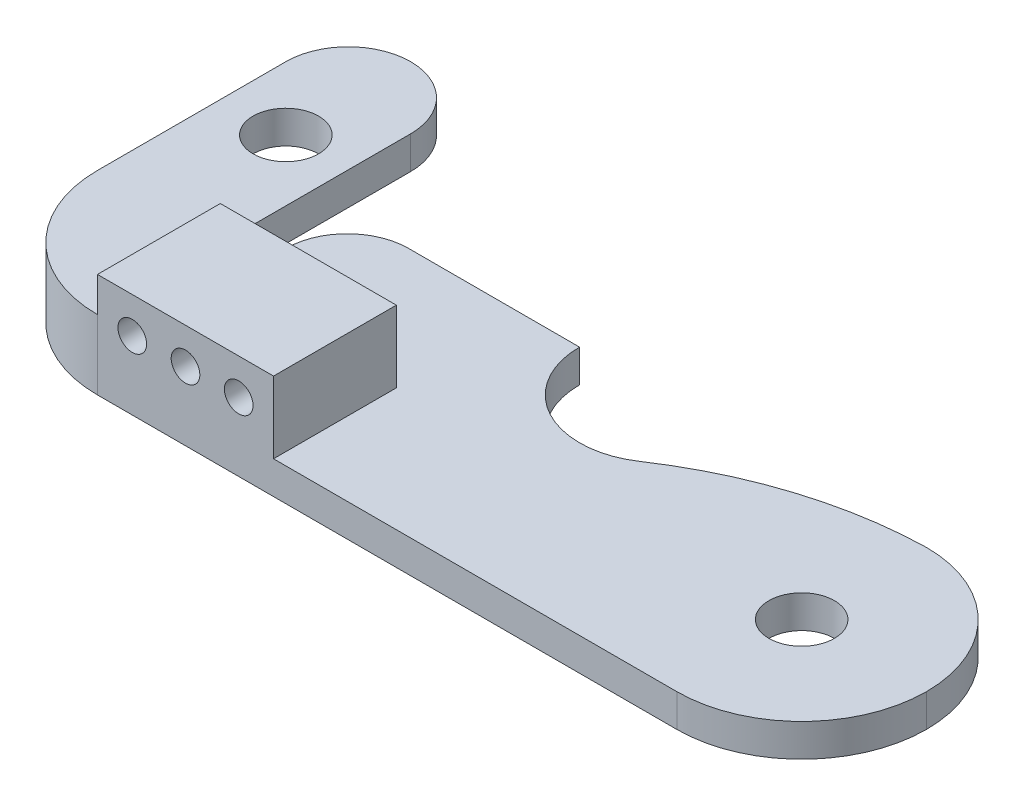
SolidWorks part; units mm, degrees
ref_plane "Front Plane" through (0, 0, 0) normal (0, 0, 1) x (1, 0, 0)
ref_plane "Top Plane" through (0, 0, 0) normal (0, 1, 0) x (1, 0, 0)
ref_plane "Right Plane" through (0, 0, 0) normal (1, 0, 0) x (0, 0, -1)
sketch "Sketch1" plane through (0, 0, 0) normal (0, 1, 0) x (1, 0, 0)
  line L0 (-13.6869, -1.9274) -> (20.7131, -1.9274)
  line L6 (-13.6869, 10.2726) -> (-13.6869, -1.9274)
  line L8 (-13.6869, 10.2726) -> (20.7131, 10.2726)
  line L10 (20.7131, 10.2726) -> (20.7131, -1.9274)
  dimension "D3" = 12.2
  dimension "D1" = 34.4
extrude "Boss-Extrude1" add sketch "Sketch1" along normal blind 1.6
sketch "Sketch8" plane through (0, 1.6, 0) normal (0, 1, 0) x (1, 0, 0)
  line L0 (5.7631, 10.2726) -> (-2.3369, 10.2726)
  line L1 (20.7131, -1.9274) -> (20.7131, 10.2726) construction
  line L2 (20.7131, -1.9274) -> (20.7131, 10.2726) construction
  line L3 (-13.6869, -1.9274) -> (20.7131, -1.9274) construction
  line L4 (20.7131, 10.2726) -> (-13.6869, 10.2726) construction
  line L6 (-13.6869, 10.2726) -> (-13.6869, -1.9274) construction
  circle A0 centre (14.6131, 4.1726) radius 1.6
  arc A1 (-2.3369, 10.2726) -> (5.7631, 10.2726) centre (1.7131, 10.2726) ccw
  dimension "D1" = 3.2
  dimension "D5" = 8.1
  dimension "D2" = 6.1
  dimension "D4" = 6.1
  dimension "D6" = 19
extrude "Cut-Extrude3" cut sketch "Sketch8" against normal through all
fillet "Fillet2" radius 3 1 edges at (-13.6869, 0.8, -10.2726)
fillet "Fillet3" radius 6.1 2 edges at (20.7131, 0.8, 1.9274) (20.7131, 0.8, -10.2726)
sketch "Sketch2" plane through (0, 1.6, 0) normal (0, 1, 0) x (1, 0, 0)
  line L1 (-13.6869, -1.9274) -> (-5.0869, -1.9274)
  line L2 (-13.6869, -1.9274) -> (-13.6869, 4.0726)
  line L3 (-13.6869, 4.0726) -> (-5.0869, 4.0726)
  line L4 (-5.0869, -1.9274) -> (-5.0869, 4.0726)
  line L5 (-13.6869, 7.2726) -> (-13.6869, -1.9274) construction
  dimension "D1" = 8.6
  dimension "D2" = 6
extrude "Boss-Extrude2" add sketch "Sketch2" along normal blind 3.5
sketch "Sketch3" plane through (0, 0, 1.9274) normal (0, 0, 1) x (1, 0, 0)
  line L0 (-5.0869, 5.1) -> (-5.0869, 1.6) construction
  line L1 (-13.6869, 5.1) -> (-5.0869, 5.1) construction
  line L2 (-13.6869, 5.1) -> (-5.0869, 5.1) construction
  line L3 (-13.6869, 5.1) -> (-13.6869, 0) construction
  circle A0 centre (-11.9869, 3.35) radius 0.7
  circle A1 centre (-6.7869, 3.35) radius 0.7
  circle A2 centre (-9.3869, 3.35) radius 0.7
  dimension "D1" = 1.4
  dimension "D2" = 1.4
  dimension "D4" = 1.4
  dimension "D3" = 1.7
  dimension "D5" = 1.75
  dimension "D6" = 1.75
  dimension "D7" = 2.6
  dimension "D8" = 1.75
  dimension "D9" = 1.7
  dimension "D10" = 2.6
extrude "Cut-Extrude1" cut sketch "Sketch3" against normal up to surface (6 mm away) up to face at (-9.3869, 3.35, -4.0726)
ref_plane "Plane1" through (0, 1.8, 0) normal (0, 1, 0) x (1, 0, 0)
sketch "Sketch4" plane through (0, 0, 0) normal (0, -1, 0) x (1, 0, 0)
  line L0 (-13.6869, 1.9274) -> (-13.6869, -4.1726)
  line L2 (-13.6869, -4.1726) -> (-19.7869, -4.1726)
  arc A0 (-13.6869, 1.9274) -> (-19.7869, -4.1726) centre (-13.6869, -4.1726) ccw
  dimension "D1" = 6.1
extrude "Boss-Extrude3" add sketch "Sketch4" against normal blind 3.4 separate body
sketch "Sketch5" plane through (0, 0, -4.1726) normal (0, 0, -1) x (-1, 0, 0)
  line L0 (19.7869, 3.4) -> (19.7869, 0) construction
  line L1 (13.6869, 3.4) -> (19.7869, 3.4)
  line L2 (13.6869, 3.4) -> (13.6869, 1.8)
  line L3 (13.6869, 1.8) -> (19.7869, 1.8)
  line L4 (19.7869, 3.4) -> (19.7869, 1.8)
extrude "Boss-Extrude4" add sketch "Sketch5" along normal blind 9.2
sketch "Sketch6" plane through (0, 3.4, 0) normal (0, 1, 0) x (1, 0, 0)
  line L0 (-19.7869, 13.3726) -> (-13.6869, 13.3726) construction
  line L1 (-19.7869, 13.3726) -> (-13.6869, 13.3726)
  arc A0 (-13.6869, 13.3726) -> (-19.7869, 13.3726) centre (-16.7369, 13.3726) ccw
extrude "Boss-Extrude5" add sketch "Sketch6" against normal up to surface (1.6 mm away) up to face at (-16.7369, 1.8, -8.7726)
sketch "Sketch7" plane through (0, 3.4, 0) normal (0, 1, 0) x (1, 0, 0)
  line L0 (-5.0869, -1.9274) -> (14.6131, -1.9274) construction
  line L2 (-19.7869, 13.3726) -> (-19.7869, 4.1726) construction
  circle A0 centre (-16.6869, 10.2726) radius 1.6
  dimension "D2" = 3.2
  dimension "D1" = 12.2
  dimension "D3" = 3.1
extrude "Cut-Extrude2" cut sketch "Sketch7" against normal up to surface (1.6 mm away) up to face at (-16.7369, 1.8, -9.5351)
fillet "Fillet1" radius 20 1 edges at (5.7631, 0.8, -10.2726)
